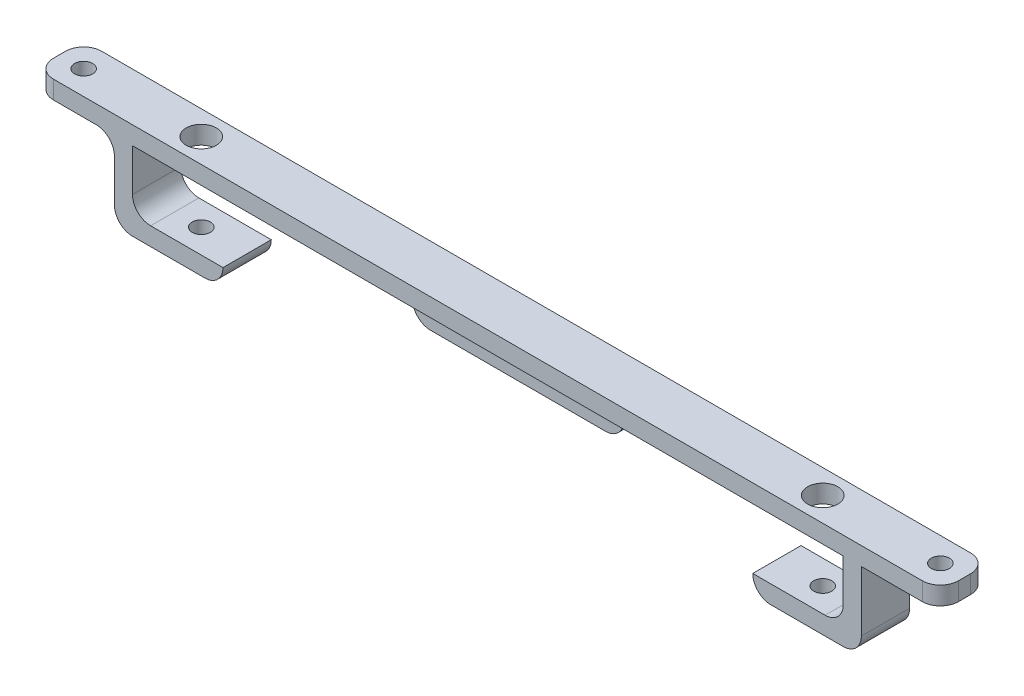
SolidWorks part; units mm, degrees
ref_plane "Front Plane" through (0, 0, 0) normal (0, 0, 1) x (1, 0, 0)
ref_plane "Top Plane" through (0, 0, 0) normal (0, 1, 0) x (1, 0, 0)
ref_plane "Right Plane" through (0, 0, 0) normal (1, 0, 0) x (0, 0, -1)
sketch "Holes Location" plane through (0, 0, 0) normal (0, 1, 0) x (1, 0, 0)
  line L0 (-51.5, 0) -> (51.5, 0)
  line L1 (-71, 0) -> (71, 0)
  dimension "D1" = 103
  dimension "D2" = 142
sketch "Sketch2" plane through (0, 0, 0) normal (0, 1, 0) x (1, 0, 0)
  line L0 (-75, 4) -> (75, -4)
  line L1 (-75, 4) -> (75, 4)
  line L2 (-75, 4) -> (-75, -4)
  line L3 (-75, -4) -> (75, -4)
  line L4 (75, 4) -> (75, -4)
  dimension "D1" = 150
  dimension "D2" = 8
extrude "Boss-Extrude1" add sketch "Sketch2" along normal blind 3 contours L2 L3 L0 | L4 L1 L0 region at (25, 0, -1.3333) region at (-25, 0, 1.3333)
sketch "Sketch3" plane through (0, 0, 0) normal (0, 0, 1) x (1, 0, 0)
  line L0 (-58.9, 0) -> (-58.9, -10)
  line L1 (-71, 0) -> (71, 0) construction
  line L2 (-58.9, -10) -> (-43.9, -10)
  line L4 (-61.9, 0) -> (-61.9, -13)
  line L5 (-61.9, -13) -> (-43.9, -13)
  line L6 (-43.9, -10) -> (-43.9, -13)
  line L7 (-58.9, 0) -> (-61.9, 0)
  dimension "D1" = 58.9
  dimension "D2" = 10
  dimension "D3" = 15
  dimension "D4" = 3
extrude "Boss-Extrude2" add sketch "Sketch3" along normal mid plane 8
sketch "Sketch4" plane through (0, 3, 0) normal (0, 1, 0) x (1, 0, 0)
  circle A0 centre (-71, 0) radius 1.5
  circle A1 centre (-51.5, 0) radius 2.5
  dimension "D1" = 3
  dimension "D2" = 5
extrude "Cut-Extrude1" cut sketch "Sketch4" against normal up to surface (3 mm away) up to face at (8.05, 0, 0)
sketch "Sketch5" plane through (0, -10, 0) normal (0, 1, 0) x (1, 0, 0)
  circle A0 centre (-51.5, 0) radius 1.5
  dimension "D1" = 3
extrude "Cut-Extrude2" cut sketch "Sketch5" against normal through all
mirror "Mirror1" about plane through (0, 0, 0) normal (1, 0, 0) of "Cut-Extrude2", "Cut-Extrude1", "Boss-Extrude2"
sketch "Sketch6" plane through (0, 0, -4) normal (0, 0, -1) x (-1, 0, 0)
  line L0 (51.5, 0) -> (-51.5, 0) construction
  line L1 (-17.5, 0) -> (17.5, 0)
  line L2 (-17.5, 0) -> (-17.5, -6.8)
  line L3 (-17.5, -6.8) -> (17.5, -6.8)
  line L4 (17.5, 0) -> (17.5, -6.8)
  dimension "D1" = 6.8
  dimension "D2" = 35
extrude "Boss-Extrude3" add sketch "Sketch6" against normal blind 3
fillet "Fillet1" radius 3 14 edges at (-43.9, -13, 0) (-58.9, -10, 0) (-61.9, -13, 0) (-61.9, 0, 0) (-75, 1.5, -4) (-75, 1.5, 4) (43.9, -13, 0) (61.9, -13, 0) (58.9, -10, 0) (75, 1.5, -4) (75, 1.5, 4) (-17.5, -6.8, -2.5) (17.5, -6.8, -2.5) (0, 0, -1)
